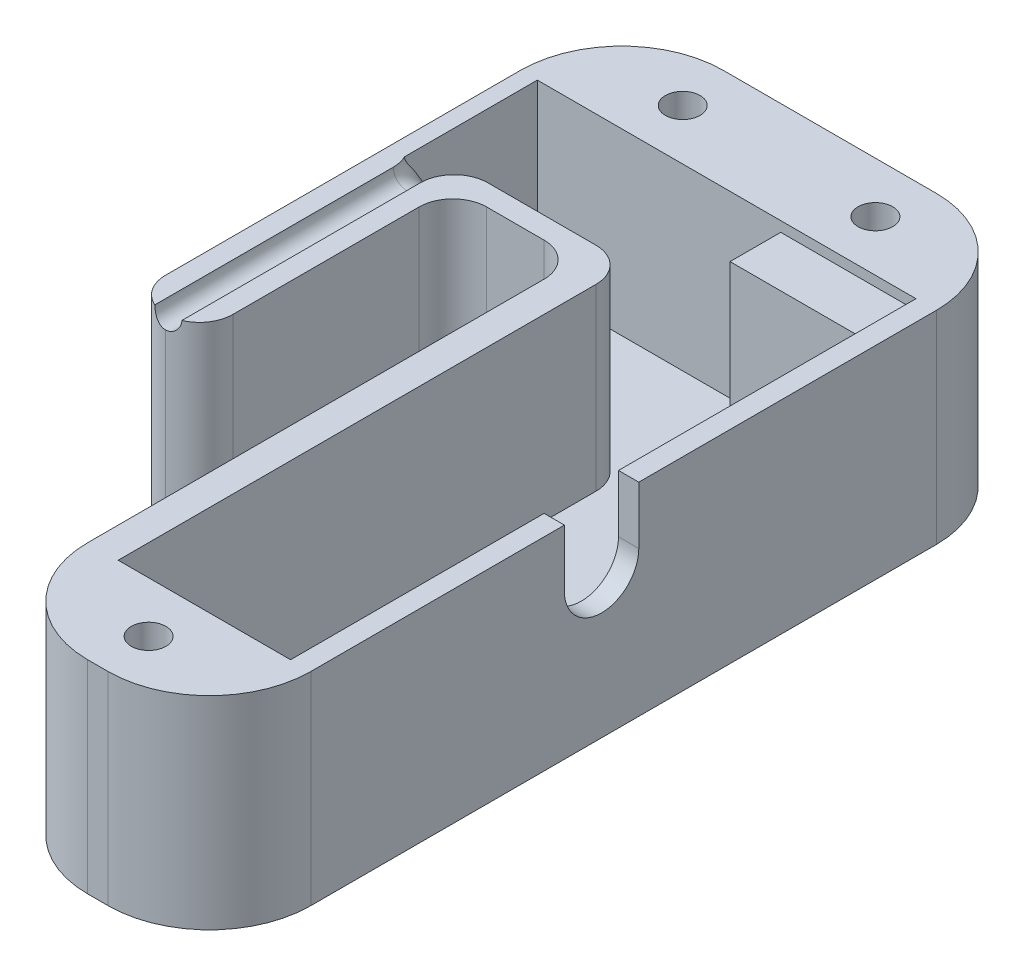
SolidWorks part; units mm, degrees
ref_plane "Front Plane" through (0, 0, 0) normal (0, 0, 1) x (1, 0, 0)
ref_plane "Top Plane" through (0, 0, 0) normal (0, 1, 0) x (1, 0, 0)
ref_plane "Right Plane" through (0, 0, 0) normal (1, 0, 0) x (0, 0, -1)
sketch "Sketch1" plane through (0, 0, 0) normal (0, 1, 0) x (1, 0, 0)
  line L0 (-16.6357, 24.6239) -> (7.9643, 24.6239)
  line L2 (-5.2357, 10.6239) -> (-5.2357, -24.3761)
  line L3 (-5.2357, -24.3761) -> (7.9643, -24.3761)
  line L4 (7.9643, 24.6239) -> (7.9643, -24.3761)
  line L7 (-5.2357, 10.6239) -> (-12.6357, 10.6239)
  line L9 (-16.6357, 24.6239) -> (-16.6357, -4.3761)
  line L12 (-16.6357, -4.3761) -> (-12.6357, -4.3761)
  line L13 (-12.6357, 10.6239) -> (-12.6357, -4.3761)
  dimension "D1" = 13.2
  dimension "D2" = 49
  dimension "D3" = 14
  dimension "D4" = 4
  dimension "D5" = 7.4
  dimension "D6" = 15
extrude "Boss-Extrude1" add sketch "Sketch1" along normal blind 12
sketch "Sketch2" plane through (0, 12, 0) normal (0, 1, 0) x (1, 0, 0)
  line L0 (7.9643, -24.3761) -> (7.9643, 24.6239) construction
  line L1 (-3.4357, -18.3761) -> (6.7643, -18.3761)
  line L2 (-3.4357, -18.3761) -> (-3.4357, 11.8984)
  line L4 (6.7643, -18.3761) -> (6.7643, 18.6239)
  line L5 (-5.2357, 10.6239) -> (-5.2357, -24.3761) construction
  line L6 (-5.2357, -24.3761) -> (7.9643, -24.3761) construction
  line L8 (-15.6357, 18.6239) -> (6.7643, 18.6239)
  line L11 (-3.4357, 11.8984) -> (-15.6357, 11.8984)
  line L12 (-15.6357, 18.6239) -> (-15.6357, 11.8984)
  line L13 (7.9643, 24.6239) -> (-16.6357, 24.6239) construction
  line L14 (-16.6357, 24.6239) -> (-16.6357, -4.3761) construction
  dimension "D1" = 1.2
  dimension "D2" = 1.8
  dimension "D3" = 6
  dimension "D4" = 6
  dimension "D5" = 1
extrude "Cut-Extrude1" cut sketch "Sketch2" against normal blind 10.6
sketch "Sketch3" plane through (0, 0, 4.3761) normal (0, 0, 1) x (1, 0, 0)
  line L0 (-16.6357, 12) -> (-12.6357, 12) construction
  circle A0 centre (-14.6357, 12) radius 0.8
  dimension "D1" = 1.6
extrude "Cut-Extrude2" cut sketch "Sketch3" against normal up to surface (16.2746 mm away) up to face at (-9.5357, 6.7, -11.8984)
sketch "Sketch4" plane through (0, 12, 0) normal (0, 1, 0) x (1, 0, 0)
  line L0 (7.9643, 24.6239) -> (-16.6357, 24.6239) construction
  line L1 (-16.6357, 24.6239) -> (-16.6357, -4.3761) construction
  line L3 (-5.2357, -24.3761) -> (7.9643, -24.3761) construction
  circle A0 centre (-10.0357, 21.6239) radius 1.025
  circle A1 centre (1.3643, 21.6239) radius 1.025
  circle A2 centre (1.3643, -21.3761) radius 1.025
  point P15 (1.3643, -24.3761)
  dimension "D1" = 2.05
  dimension "D2" = 2.05
  dimension "D3" = 2.05
  dimension "D4" = 3
  dimension "D5" = 3
  dimension "D6" = 6.6
  dimension "D8" = 3
extrude "Cut-Extrude3" cut sketch "Sketch4" against normal blind 6
fillet "Fillet1" radius 6 4 edges at (-5.2357, 6, 24.3761) (7.9643, 6, 24.3761) (7.9643, 6, -24.6239) (-16.6357, 6, -24.6239)
fillet "Fillet2" radius 2 4 edges at (-5.2357, 6, -10.6239) (-12.6357, 6, -10.6239) (-12.6357, 6, 4.3761) (-16.6357, 6, 4.3761)
sketch "Sketch5" plane through (7.9643, 0, 0) normal (1, 0, 0) x (0, 0, -1)
  line L0 (-18.3761, 0) -> (18.6239, 0) construction
  line L1 (-18.3761, 12) -> (-18.3761, 0) construction
  line L2 (-3.3761, 8.6) -> (-3.3761, 12)
  line L3 (-18.3761, 12) -> (18.6239, 12) construction
  line L4 (-3.3761, 12) -> (1.0239, 12)
  line L5 (1.0239, 12) -> (1.0239, 8.6)
  arc A0 (-3.3761, 8.6) -> (1.0239, 8.6) centre (-1.1761, 8.6) ccw
  dimension "D1" = 4.4
  dimension "D2" = 8.6
  dimension "D3" = 17.2
extrude "Cut-Extrude4" cut sketch "Sketch5" against normal up to surface (1.2 mm away) up to face at (6.7643, 6.7, -0.1239)
fillet "Fillet3" radius 2 2 edges at (-14.6357, 11.2, -11.8984) (-3.4357, 6.7, -11.8984)
sketch "Sketch6" plane through (0, 1.4, 0) normal (0, 1, 0) x (1, 0, 0)
  line L1 (6.7643, 18.6239) -> (-1.2357, 18.6239)
  line L2 (6.7643, 18.6239) -> (6.7643, 15.6239)
  line L3 (6.7643, 15.6239) -> (-1.2357, 15.6239)
  line L4 (-1.2357, 18.6239) -> (-1.2357, 15.6239)
  dimension "D1" = 8
  dimension "D2" = 3
extrude "Boss-Extrude2" add sketch "Sketch6" along normal blind 10
